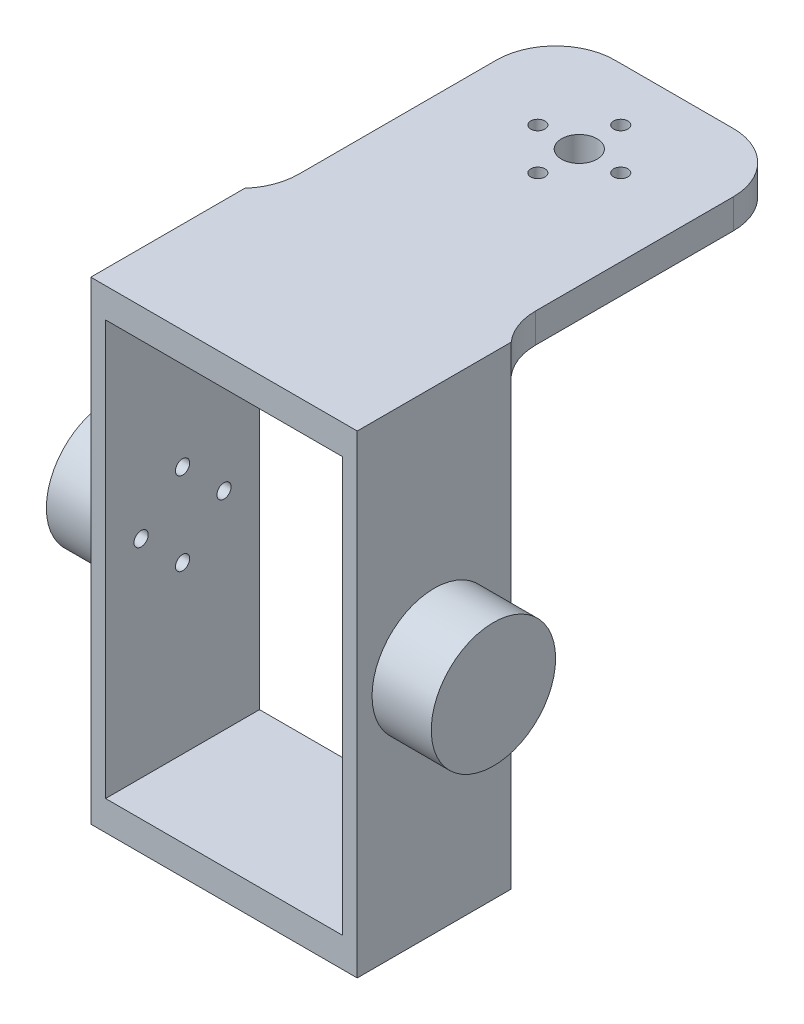
SolidWorks part; units mm, degrees
ref_plane "Front Plane" through (0, 0, 0) normal (0, 0, 1) x (1, 0, 0)
ref_plane "Top Plane" through (0, 0, 0) normal (0, 1, 0) x (1, 0, 0)
ref_plane "Right Plane" through (0, 0, 0) normal (1, 0, 0) x (0, 0, -1)
sketch "Sketch1" plane through (0, 0, 0) normal (0, 1, 0) x (1, 0, 0)
  line L1 (0, 0) -> (45, 0)
  line L2 (0, 0) -> (0, 26)
  line L3 (0, 26) -> (45, 26)
  line L4 (45, 0) -> (45, 26)
  dimension "D1" = 45
  dimension "D2" = 26
extrude "Boss-Extrude1" add sketch "Sketch1" along normal blind 5
sketch "Sketch2" plane through (0, 5, 0) normal (0, 1, 0) x (1, 0, 0)
  line L0 (0, 0) -> (45, 0) construction
  line L1 (0, 26) -> (2.5, 26)
  line L2 (0, 26) -> (0, 0)
  line L3 (0, 0) -> (2.5, 0)
  line L4 (2.5, 26) -> (2.5, 0)
  dimension "D1" = 2.5
extrude "Boss-Extrude2" add sketch "Sketch2" along normal blind 70
pattern_linear "LPattern2" count 2 spacing 42.5 along (1, 0, 0) of "Boss-Extrude2"
sketch "Sketch3" plane through (0, 75, 0) normal (0, 1, 0) x (1, 0, 0)
  line L1 (0, 26) -> (45, 26)
  line L2 (0, 26) -> (0, 0)
  line L3 (0, 0) -> (45, 0)
  line L4 (45, 26) -> (45, 0)
extrude "Boss-Extrude3" add sketch "Sketch3" along normal blind 5
sketch "Sketch7" plane through (0, 0, 0) normal (-1, 0, 0) x (0, 0, 1)
  line L0 (-26, 80) -> (-26, 0) construction
  line L2 (-26, 80) -> (0, 80) construction
  circle A0 centre (-13, 40) radius 10.5
  point P4 (0, 0)
  point P5 (0, 0)
  point P6 (12.806, -9.8375)
  dimension "D2" = 21
  dimension "D1" = 13
  dimension "D3" = 40
extrude "Boss-Extrude5" add sketch "Sketch7" along normal blind 10
pattern_linear "LPattern3" count 2 spacing 50 along (1, 0, 0) of "Boss-Extrude5"
sketch "Sketch8" plane through (-10, 0, 0) normal (-1, 0, 0) x (0, 0, 1)
  line L0 (-26, 80) -> (-26, 0) construction
  circle A0 centre (-13, 47) radius 1.2
  circle A1 centre (-13, 40) radius 10.5 construction
  dimension "D3" = 2.4
  dimension "D1" = 7
  dimension "D2" = 13
extrude "Cut-Extrude1" cut sketch "Sketch8" against normal up to next
pattern_circular "CirPattern1" count 4 over 360 about axis through (-10, 40, -13) along (-1, 0, 0) of "Cut-Extrude1"
sketch "Sketch9" plane through (-10, 0, 0) normal (-1, 0, 0) x (0, 0, 1)
  circle A0 centre (-13, 40) radius 3
  dimension "D1" = 6
extrude "Cut-Extrude2" cut sketch "Sketch9" against normal blind 2
sketch "Sketch10" plane through (50, 0, 0) normal (1, 0, 0) x (0, 0, -1)
  circle A0 centre (13, 40) radius 10.5
  dimension "D1" = 21
extrude "Boss-Extrude6" add sketch "Sketch10" along normal blind 5
sketch "Sketch11" plane through (0, 0, -26) normal (0, 0, -1) x (-1, 0, 0)
  line L0 (-45, 80) -> (0, 80) construction
  line L1 (-2.5, 75) -> (-42.5, 75)
  line L2 (-2.5, 75) -> (-2.5, 80)
  line L3 (-2.5, 80) -> (-42.5, 80)
  line L4 (-42.5, 75) -> (-42.5, 80)
extrude "Boss-Extrude7" add sketch "Sketch11" along normal blind 50
fillet "Fillet1" radius 10 4 edges at (2.5, 77.5, -26) (42.5, 77.5, -26) (2.5, 77.5, -76) (42.5, 77.5, -76)
sketch "Sketch12" plane through (0, 80, 0) normal (0, 1, 0) x (1, 0, 0)
  line L0 (2.5, 66) -> (2.5, 32.6144) construction
  line L2 (12.5, 76) -> (32.5, 76) construction
  circle A0 centre (22.5, 60) radius 3
  circle A1 centre (29.5, 60) radius 1.2
  dimension "D3" = 6
  dimension "D4" = 2.4
  dimension "D1" = 20
  dimension "D2" = 16
  dimension "D5" = 7
extrude "Cut-Extrude3" cut sketch "Sketch12" against normal blind 50
pattern_circular "CirPattern2" count 4 over 360 about axis through (22.5, 80, -60) along (0, 1, 0) of "Cut-Extrude3"
